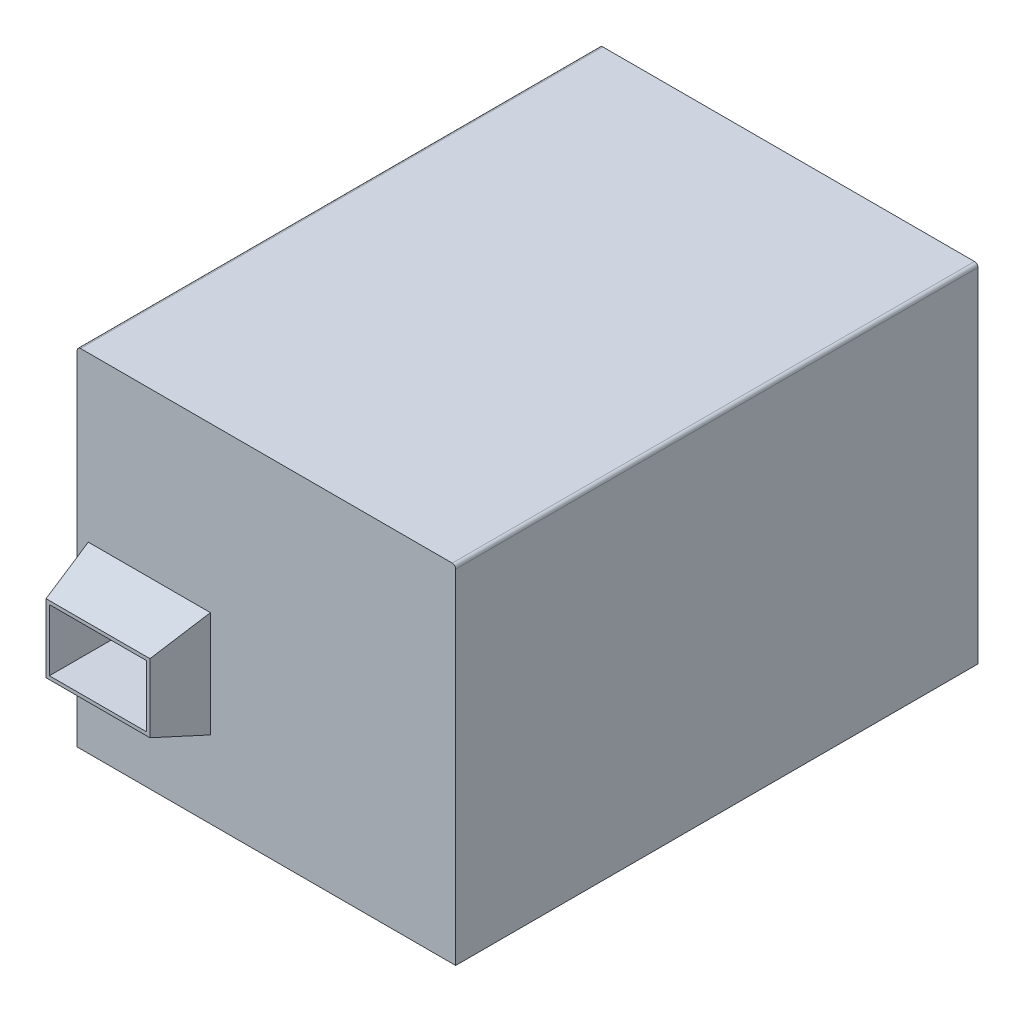
SolidWorks part; units mm, degrees
material "2195 Aluminum"
ref_plane "Front Plane" through (0, 0, 0) normal (0, 0, 1) x (1, 0, 0)
ref_plane "Top Plane" through (0, 0, 0) normal (0, 1, 0) x (1, 0, 0)
ref_plane "Right Plane" through (0, 0, 0) normal (1, 0, 0) x (0, 0, -1)
sketch "Sketch1" plane through (0, 0, 0) normal (0, 0, 1) x (1, 0, 0)
  line L0 (-467.5, -393.75) -> (-467.5, 493.75)
  line L1 (-530, -456.25) -> (575, -456.25)
  line L2 (-530, -456.25) -> (-530, 556.25)
  line L3 (-530, 556.25) -> (575, 556.25)
  line L4 (575, -456.25) -> (575, 556.25)
  line L5 (-467.5, -231.25) -> (512.5, -231.25)
  line L6 (512.5, -231.25) -> (512.5, -293.75)
  line L7 (-467.5, -393.75) -> (512.5, -393.75)
  line L11 (512.5, -293.75) -> (-467.5, -293.75)
  line L12 (-467.5, -293.75) -> (-467.5, -231.25)
  line L13 (-467.5, 493.75) -> (512.5, 493.75)
  line L14 (512.5, 493.75) -> (512.5, -393.75)
  line L15 (-467.5, 293.75) -> (512.5, 293.75)
  line L16 (512.5, 293.75) -> (512.5, 231.25)
  line L17 (512.5, 231.25) -> (-467.5, 231.25)
  line L18 (-467.5, 231.25) -> (-467.5, 293.75)
  line L19 (-182.5, 493.75) -> (-182.5, -393.75)
  line L20 (-182.5, -393.75) -> (-120, -393.75)
  line L21 (-120, -393.75) -> (-120, 493.75)
  line L22 (-120, 493.75) -> (-182.5, 493.75)
  line L24 (165, 493.75) -> (227.5, 493.75)
  line L25 (165, 493.75) -> (165, -393.75)
  line L26 (165, -393.75) -> (227.5, -393.75)
  line L27 (227.5, 493.75) -> (227.5, -393.75)
  line L28 (-467.5, 31.25) -> (512.5, 31.25)
  line L29 (-467.5, 31.25) -> (-467.5, -31.25)
  line L30 (-467.5, -31.25) -> (512.5, -31.25)
  line L31 (512.5, 31.25) -> (512.5, -31.25)
  point P0 (0, 0)
  point P6 (3.1071, -2.3383)
  dimension "D1" = 1105
  dimension "D2" = 1012.5
  dimension "D3" = 62.5
  dimension "D4" = 200
  dimension "D5" = 62.5
  dimension "D6" = 62.5
  dimension "D7" = 285
  dimension "D8" = 285
  dimension "D9" = 62.5
  dimension "D10" = 62.5
  dimension "D11" = 200
  dimension "D12" = 62.5
  dimension "D13" = 62.5
  dimension "D14" = 62.5
  dimension "D15" = 456.25
  dimension "D16" = 575
  dimension "D17" = 62.5
  dimension "D18" = 200
extrude "Boss-Extrude1" add sketch "Sketch1" against normal blind 1400 contours L1 L4 L3 L2 L13 L14 L7 L0 | L19 L15 L0 L17 | L17 L21 L15 L19 | L15 L21 L13 L19 | L25 L15 L21 L17 | L27 L13 L25 L15 | L27 L15 L25 L17 | L15 L27 L17 L14 | L27 L30 L14 L28 | L25 L28 L27 L17 | L25 L30 L27 L28 | L30 L25 L7 L27 | L21 L30 L25 L28 | L19 L28 L21 L17 | L19 L30 L21 L28 | L0 L30 L19 L28 | L30 L19 L7 L21 | L30 L19 L5 L21 | L19 L5 L0 L11 | L25 L5 L21 L11 | L30 L25 L5 L27 | L5 L27 L11 L6
sketch "Sketch2" plane through (0, 0, -1400) normal (0, 0, -1) x (-1, 0, 0)
  line L0 (530, -456.25) -> (530, 556.25) construction
  line L1 (-575, -456.25) -> (530, -456.25)
  line L2 (-575, -456.25) -> (-575, 556.25)
  line L3 (-575, 556.25) -> (530, 556.25)
  line L4 (530, -456.25) -> (530, 556.25)
  line L5 (-575, -456.25) -> (-575, 556.25) construction
  line L6 (530, -456.25) -> (-575, -456.25) construction
  line L7 (530, 556.25) -> (-575, 556.25) construction
  point P0 (0, 0)
extrude "Boss-Extrude3" add sketch "Sketch2" along normal blind 62.5
sketch "Sketch3" plane through (0, 0, 0) normal (0, 0, 1) x (1, 0, 0)
  line L0 (512.5, 493.75) -> (512.5, 293.75) construction
  line L1 (-467.5, -393.75) -> (512.5, -393.75)
  line L2 (-467.5, -393.75) -> (-467.5, 493.75)
  line L3 (-467.5, 493.75) -> (512.5, 493.75)
  line L4 (512.5, -393.75) -> (512.5, 493.75)
  line L5 (-467.5, 31.25) -> (-467.5, 231.25) construction
  line L6 (-467.5, -393.75) -> (512.5, -393.75) construction
  line L7 (227.5, 493.75) -> (512.5, 493.75) construction
  point P0 (0, 0)
extrude "Cut-Extrude1" cut sketch "Sketch3" against normal blind 700
sketch "Sketch4" plane through (0, 0, -700) normal (0, 0, 1) x (1, 0, 0)
  line L0 (-467.5, 293.75) -> (-467.5, 493.75) construction
  line L1 (-357.5, 293.75) -> (-292.5, 293.75)
  line L2 (-357.5, 293.75) -> (-357.5, 303.75)
  line L3 (-357.5, 303.75) -> (-292.5, 303.75)
  line L4 (-292.5, 293.75) -> (-292.5, 303.75)
  line L5 (-407.5, 293.75) -> (-467.5, 293.75)
  line L6 (-407.5, 293.75) -> (-407.5, 303.75)
  line L7 (-407.5, 303.75) -> (-467.5, 303.75)
  line L8 (-467.5, 293.75) -> (-467.5, 303.75)
  line L9 (-242.5, 293.75) -> (-182.5, 293.75)
  line L10 (-242.5, 293.75) -> (-242.5, 303.75)
  line L11 (-242.5, 303.75) -> (-182.5, 303.75)
  line L12 (-182.5, 293.75) -> (-182.5, 303.75)
  line L13 (-182.5, 493.75) -> (-182.5, 293.75) construction
  line L14 (-467.5, 293.75) -> (-182.5, 293.75) construction
  line L15 (-151.25, 369.4837) -> (-151.25, 227.0434) construction
  line L16 (-182.5, 493.75) -> (-182.5, 293.75) construction
  line L17 (-120, 293.75) -> (-120, 303.75)
  line L18 (-60, 303.75) -> (-120, 303.75)
  line L19 (-60, 293.75) -> (-120, 293.75)
  line L20 (-60, 293.75) -> (-60, 303.75)
  line L21 (-10, 293.75) -> (-10, 303.75)
  line L22 (55, 293.75) -> (-10, 293.75)
  line L23 (55, 303.75) -> (-10, 303.75)
  line L24 (55, 293.75) -> (55, 303.75)
  line L25 (165, 293.75) -> (165, 303.75)
  line L26 (105, 293.75) -> (165, 293.75)
  line L27 (105, 293.75) -> (105, 303.75)
  line L28 (105, 303.75) -> (165, 303.75)
  line L29 (196.25, 369.4837) -> (196.25, 272.2773) construction
  line L30 (165, 493.75) -> (165, 293.75) construction
  line L31 (287.5, 293.75) -> (287.5, 303.75)
  line L32 (287.5, 293.75) -> (227.5, 293.75)
  line L33 (227.5, 293.75) -> (227.5, 303.75)
  line L34 (287.5, 303.75) -> (227.5, 303.75)
  line L35 (402.5, 293.75) -> (402.5, 303.75)
  line L36 (337.5, 293.75) -> (402.5, 293.75)
  line L37 (337.5, 293.75) -> (337.5, 303.75)
  line L38 (337.5, 303.75) -> (402.5, 303.75)
  line L39 (452.5, 293.75) -> (452.5, 303.75)
  line L40 (452.5, 293.75) -> (512.5, 293.75)
  line L41 (512.5, 293.75) -> (512.5, 303.75)
  line L42 (452.5, 303.75) -> (512.5, 303.75)
  line L43 (-467.5, 31.25) -> (-467.5, 41.25)
  line L44 (-407.5, 41.25) -> (-467.5, 41.25)
  line L45 (-407.5, 31.25) -> (-467.5, 31.25)
  line L46 (-407.5, 31.25) -> (-407.5, 41.25)
  line L47 (-357.5, 31.25) -> (-292.5, 31.25)
  line L48 (-357.5, 41.25) -> (-292.5, 41.25)
  line L49 (-357.5, 31.25) -> (-357.5, 41.25)
  line L50 (-292.5, 31.25) -> (-292.5, 41.25)
  line L51 (-242.5, 41.25) -> (-182.5, 41.25)
  line L52 (-242.5, 31.25) -> (-242.5, 41.25)
  line L53 (-242.5, 31.25) -> (-182.5, 31.25)
  line L54 (-182.5, 31.25) -> (-182.5, 41.25)
  line L55 (-60, 41.25) -> (-120, 41.25)
  line L56 (-60, 31.25) -> (-60, 41.25)
  line L57 (-60, 31.25) -> (-120, 31.25)
  line L58 (-120, 31.25) -> (-120, 41.25)
  line L59 (-10, 31.25) -> (-10, 41.25)
  line L60 (55, 41.25) -> (-10, 41.25)
  line L61 (55, 31.25) -> (-10, 31.25)
  line L62 (105, 31.25) -> (105, 41.25)
  line L63 (55, 31.25) -> (55, 41.25)
  line L64 (105, 41.25) -> (165, 41.25)
  line L65 (105, 31.25) -> (165, 31.25)
  line L66 (165, 31.25) -> (165, 41.25)
  line L67 (287.5, 41.25) -> (227.5, 41.25)
  line L68 (287.5, 31.25) -> (287.5, 41.25)
  line L69 (287.5, 31.25) -> (227.5, 31.25)
  line L70 (227.5, 31.25) -> (227.5, 41.25)
  line L71 (337.5, 41.25) -> (402.5, 41.25)
  line L72 (402.5, 31.25) -> (402.5, 41.25)
  line L73 (337.5, 31.25) -> (402.5, 31.25)
  line L74 (337.5, 31.25) -> (337.5, 41.25)
  line L75 (452.5, 41.25) -> (512.5, 41.25)
  line L76 (512.5, 31.25) -> (512.5, 41.25)
  line L77 (452.5, 31.25) -> (512.5, 31.25)
  line L78 (452.5, 31.25) -> (452.5, 41.25)
  line L79 (-467.5, -231.25) -> (-467.5, -221.25)
  line L80 (-407.5, -221.25) -> (-467.5, -221.25)
  line L81 (-407.5, -231.25) -> (-467.5, -231.25)
  line L82 (-407.5, -231.25) -> (-407.5, -221.25)
  line L83 (-357.5, -231.25) -> (-292.5, -231.25)
  line L84 (-357.5, -221.25) -> (-292.5, -221.25)
  line L85 (-357.5, -231.25) -> (-357.5, -221.25)
  line L86 (-292.5, -231.25) -> (-292.5, -221.25)
  line L87 (-242.5, -221.25) -> (-182.5, -221.25)
  line L88 (-242.5, -231.25) -> (-242.5, -221.25)
  line L89 (-242.5, -231.25) -> (-182.5, -231.25)
  line L90 (-182.5, -231.25) -> (-182.5, -221.25)
  line L91 (-60, -221.25) -> (-120, -221.25)
  line L92 (-60, -231.25) -> (-60, -221.25)
  line L93 (-60, -231.25) -> (-120, -231.25)
  line L94 (-120, -231.25) -> (-120, -221.25)
  line L95 (-10, -231.25) -> (-10, -221.25)
  line L96 (55, -221.25) -> (-10, -221.25)
  line L97 (55, -231.25) -> (-10, -231.25)
  line L98 (105, -231.25) -> (105, -221.25)
  line L99 (55, -231.25) -> (55, -221.25)
  line L100 (105, -221.25) -> (165, -221.25)
  line L101 (105, -231.25) -> (165, -231.25)
  line L102 (165, -231.25) -> (165, -221.25)
  line L103 (287.5, -221.25) -> (227.5, -221.25)
  line L104 (287.5, -231.25) -> (287.5, -221.25)
  line L105 (287.5, -231.25) -> (227.5, -231.25)
  line L106 (227.5, -231.25) -> (227.5, -221.25)
  line L107 (337.5, -221.25) -> (402.5, -221.25)
  line L108 (402.5, -231.25) -> (402.5, -221.25)
  line L109 (337.5, -231.25) -> (402.5, -231.25)
  line L110 (337.5, -231.25) -> (337.5, -221.25)
  line L111 (452.5, -221.25) -> (512.5, -221.25)
  line L112 (512.5, -231.25) -> (512.5, -221.25)
  line L113 (452.5, -231.25) -> (512.5, -231.25)
  line L114 (452.5, -231.25) -> (452.5, -221.25)
  point P12 (-357.5, 298.75)
  dimension "D1" = 50
  dimension "D2" = 50
  dimension "D3" = 10
  dimension "D4" = 65
  dimension "D5" = 31.25
  dimension "D6" = 31.25
  dimension "D7" = 3
sketch "Sketch5" plane through (0, 0, -700) normal (0, 0, 1) x (1, 0, 0)
  line L0 (-467.5, -393.75) -> (512.5, -393.75) construction
  line L1 (-467.5, -393.75) -> (512.5, -393.75)
  line L2 (-467.5, -393.75) -> (-467.5, -293.75)
  line L3 (-467.5, -293.75) -> (512.5, -293.75)
  line L4 (512.5, -393.75) -> (512.5, -293.75)
  line L5 (-467.5, -393.75) -> (-467.5, 493.75) construction
  line L6 (512.5, -293.75) -> (-467.5, -293.75) construction
  line L7 (512.5, 493.75) -> (512.5, -393.75) construction
extrude "Boss-Extrude4" add sketch "Sketch5" against normal up to next
extrude "Boss-Extrude5" add sketch "Sketch4" against normal blind 10
fillet "Fillet1" radius 10 2 edges at (-530, 556.25, -731.25) (575, 556.25, -731.25)
sketch "Sketch6" plane through (0, 0, 0) normal (0, 0, 1) x (1, 0, 0)
  line L0 (-520, 556.25) -> (565, 556.25) construction
  line L1 (-530, -456.25) -> (575, -456.25)
  line L2 (-530, -456.25) -> (-530, 546.25)
  line L3 (-520, 556.25) -> (565, 556.25)
  line L4 (575, -456.25) -> (575, 546.25)
  line L5 (-530, -456.25) -> (-530, 546.25) construction
  line L6 (-530, -456.25) -> (575, -456.25) construction
  line L7 (575, -456.25) -> (575, 546.25) construction
  arc A0 (565, 556.25) -> (575, 546.25) centre (565, 546.25) cw
  arc A1 (-530, 546.25) -> (-520, 556.25) centre (-520, 546.25) cw
  dimension "D1" = 10
extrude "Boss-Extrude6" add sketch "Sketch6" along normal blind 62.5
sketch "Sketch8" plane through (-530, 0, 0) normal (-1, 0, 0) x (0, 0, 1)
  line L0 (62.5, 77.9411) -> (212.5, 23.3455)
  line L1 (212.5, 23.3455) -> (212.5, -176.6545)
  line L2 (212.5, -176.6545) -> (62.5, -231.25)
  line L3 (62.5, -231.25) -> (62.5, 77.9411)
  line L4 (62.5, 546.25) -> (62.5, -456.25) construction
  line L5 (-1462.5, -456.25) -> (62.5, -456.25) construction
  dimension "D1" = 200
  dimension "D2" = 225
  dimension "D3" = 150
  dimension "D4" = 70
  dimension "D5" = 70
extrude "Boss-Extrude7" add sketch "Sketch8" against normal blind 300 from offset 62.5 offset against normal yes
chamfer "Chamfer1" [suppressed] distance 70 angle 20
sketch "Sketch9" [suppressed] plane through (0, 0, 212.5) normal (0, 0, 1) x (1, 0, 0)
  line L1 (-125.3784, 23.3455) -> (-196.6176, 23.3455)
  line L2 (-125.3784, 23.3455) -> (-125.3784, -176.6545)
  line L3 (-125.3784, -176.6545) -> (-196.6176, -176.6545)
  line L4 (-196.6176, 23.3455) -> (-196.6176, -176.6545)
  line L5 (-167.5, 23.3455) -> (-467.5, 23.3455) construction
  line L6 (-125.3784, -176.6545) -> (-125.3784, 23.3455) construction
  line L7 (-167.5, -176.6545) -> (-467.5, -176.6545) construction
  line L8 (-196.6176, -176.6545) -> (-196.6176, 23.3455) construction
extrude "Cut-Extrude2" [suppressed] cut sketch "Sketch9" against normal blind 200
sketch "Sketch10" [suppressed] plane through (-467.5, 0, 0) normal (1, 0, 0) x (0, 0, -1)
  line L0 (67.5, -51.6545) -> (67.5, -101.6545)
  line L1 (67.5, -101.6545) -> (77.5, -101.6545)
  line L2 (77.5, -101.6545) -> (77.5, -51.6545)
  line L3 (77.5, -51.6545) -> (67.5, -51.6545)
  line L5 (0, -393.75) -> (0, 493.75) construction
  line L8 (-62.5, 23.3455) -> (-12.5, 23.3455) construction
  line L9 (-62.5, -176.6545) -> (-12.5, -176.6545) construction
  line L11 (77.5, -101.6545) -> (0, -101.6545)
  line L12 (77.5, -101.6545) -> (77.5, -91.6545)
  line L13 (77.5, -91.6545) -> (0, -91.6545)
  line L14 (0, -101.6545) -> (0, -91.6545)
  line L15 (77.5, -51.6545) -> (0, -51.6545)
  line L16 (77.5, -51.6545) -> (77.5, -61.6545)
  line L17 (77.5, -61.6545) -> (0, -61.6545)
  line L18 (0, -51.6545) -> (0, -61.6545)
  line M6 (0, 493.75) -> (0, -393.75)
  line M10 (0, 493.75) -> (0, -393.75)
  dimension "D1" = 67.5
  dimension "D2" = 125
  dimension "D3" = 10
  dimension "D4" = 125
  dimension "D5" = 10
  dimension "D6" = 10
extrude "Boss-Extrude8" [suppressed] add sketch "Sketch10" along normal blind 325 contours L12 L13 L11 L1 M6 | L3 L2 L1 L0 | L17 L16 L3 L15 M10
sketch "Sketch13" [suppressed] plane through (0, 0, 62.5) normal (0, 0, 1) x (1, 0, 0)
  line L0 (-467.5, -221.9768) -> (-467.5, 68.6679) construction
  line L1 (-467.5, -176.6545) -> (-196.6176, -176.6545)
  line L2 (-467.5, -176.6545) -> (-467.5, 23.3455)
  line L3 (-467.5, 23.3455) -> (-196.6176, 23.3455)
  line L4 (-196.6176, -176.6545) -> (-196.6176, 23.3455)
  line L5 (-196.6176, 23.3455) -> (-167.5, 23.3455) construction
  line L6 (-196.6176, -176.6545) -> (-196.6176, 23.3455) construction
  line L7 (-167.5, -176.6545) -> (-196.6176, -176.6545) construction
extrude "Cut-Extrude3" [suppressed] cut sketch "Sketch13" against normal blind 172
chamfer "Chamfer3" distance 150 angle 10 1 edges at (-167.5, -76.6545, 62.5)
chamfer "Chamfer4" distance 30 angle 80 1 edges at (-467.5, -76.6545, 62.5)
sketch "Sketch14" plane through (0, 0, 212.5) normal (0, 0, 1) x (1, 0, 0)
  line L0 (-167.5, 23.3455) -> (-471.051, 23.3455) construction
  line L1 (-461.051, 13.3455) -> (-177.5, 13.3455)
  line L2 (-461.051, 13.3455) -> (-461.051, -166.6545)
  line L3 (-461.051, -166.6545) -> (-177.5, -166.6545)
  line L4 (-177.5, 13.3455) -> (-177.5, -166.6545)
  line L5 (-167.5, -176.6545) -> (-167.5, 23.3455) construction
  line L6 (-167.5, -176.6545) -> (-471.051, -176.6545) construction
  line L7 (-471.051, 23.3455) -> (-471.051, -176.6545) construction
  dimension "D1" = 10
  dimension "D2" = 10
  dimension "D3" = 10
  dimension "D4" = 10
extrude "Cut-Extrude4" cut sketch "Sketch14" against normal blind 259
sketch "Sketch15" plane through (575, 0, 0) normal (1, 0, 0) x (0, 0, -1)
ref_plane "Plane1" through (0, 50, 0) normal (0, 1, 0) x (1, 0, 0)
sketch "Sketch16" plane through (0, 50, 0) normal (0, 1, 0) x (1, 0, 0)
  circle A0 centre (0, 651.7396) radius 3000
  point P2 (0, 651.7396)
  dimension "D1" = 6000
equation "\"D2@Sketch1\"=600+(5*(62.5))+100"
equation "\"D1@Sketch1\"=(3*(285))+(4*(62.5))"
equation "\"D5@Sketch4\"=62.5/2"
